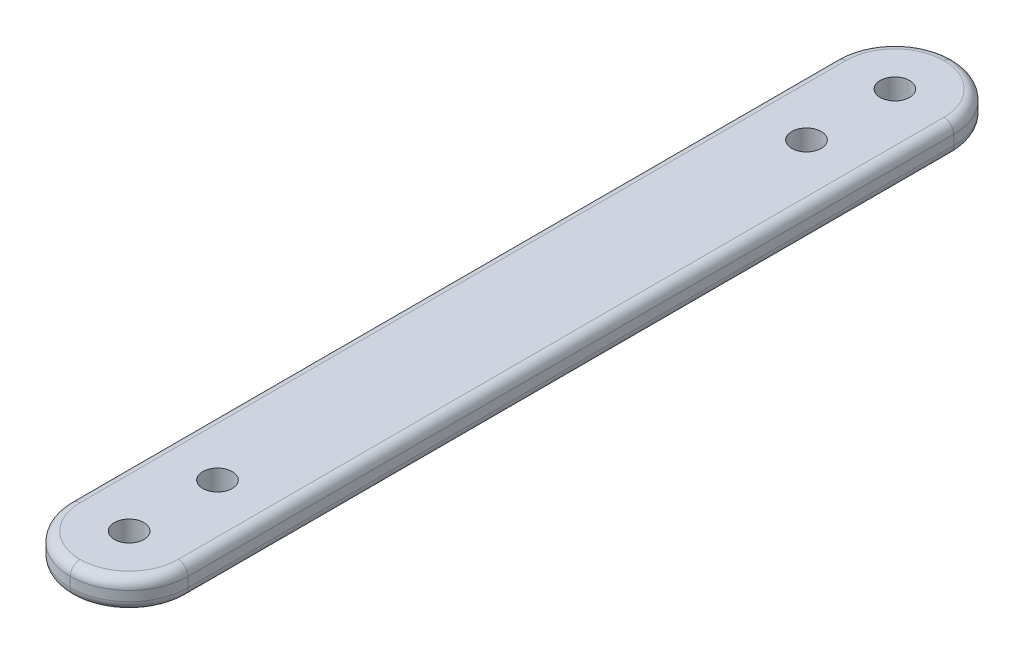
SolidWorks part; units mm, degrees
material "6061 Alloy"
ref_plane "Front Plane" through (0, 0, 0) normal (0, 0, 1) x (1, 0, 0)
ref_plane "Top Plane" through (0, 0, 0) normal (0, 1, 0) x (1, 0, 0)
ref_plane "Right Plane" through (0, 0, 0) normal (1, 0, 0) x (0, 0, -1)
sketch "Sketch1" plane through (0, 0, 0) normal (0, 1, 0) x (1, 0, 0)
  line L0 (0, 95.25) -> (0, -95.25) construction
  line L1 (-12.7, -95.25) -> (12.7, -95.25)
  line L2 (-12.7, -95.25) -> (-12.7, 95.25)
  line L3 (-12.7, 95.25) -> (12.7, 95.25)
  line L4 (12.7, -95.25) -> (12.7, 95.25)
  line L5 (-12.7, -95.25) -> (12.7, 95.25) construction
  line L6 (-12.7, 95.25) -> (12.7, -95.25) construction
  circle A0 centre (0, -82.55) radius 3.175
  circle A1 centre (0, 63.5) radius 3.175
  circle A2 centre (0, 82.55) radius 3.175
  circle A3 centre (0, -63.5) radius 3.175
  point P0 (0, 0)
  dimension "D3" = 6.35
  dimension "D1" = 6.35
  dimension "D8" = 127
  dimension "D2" = 25.4
  dimension "D4" = 19.05
  dimension "D5" = 19.05
  dimension "D6" = 12.7
  dimension "D7" = 12.7
extrude "Boss-Extrude1" add sketch "Sketch1" along normal blind 6.35
fillet "Fillet2" radius 12.7 4 edges at (-12.7, 3.175, -95.25) (12.7, 3.175, -95.25) (-12.7, 3.175, 95.25) (12.7, 3.175, 95.25)
fillet "Fillet3" radius 2.1167 12 edges at (8.9803, 6.35, 91.5303) (-8.9803, 6.35, 91.5303) (-12.7, 6.35, 0) (-8.9803, 6.35, -91.5303) (8.9803, 6.35, -91.5303) (8.9803, 0, 91.5303) (-8.9803, 0, 91.5303) (-12.7, 0, 0) (-8.9803, 0, -91.5303) (8.9803, 0, -91.5303) (12.7, 6.35, 0) (12.7, 0, 0)
